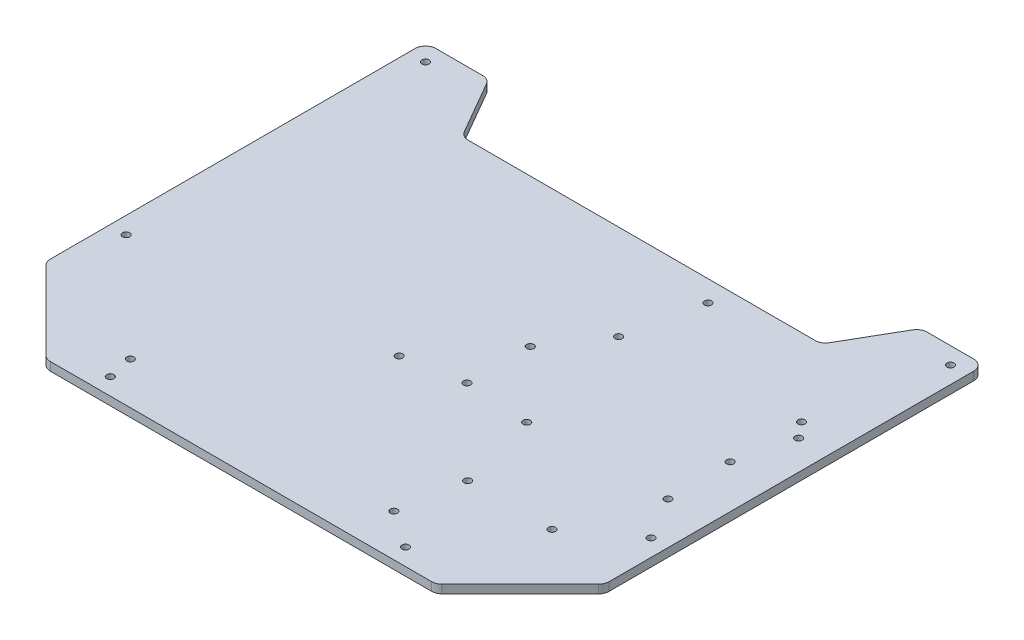
SolidWorks part; units mm, degrees
material "Acier non allié"
ref_plane "Front" through (0, 0, 0) normal (0, 0, 1) x (1, 0, 0)
ref_plane "Top" through (0, 0, 0) normal (0, 1, 0) x (1, 0, 0)
ref_plane "Right" through (0, 0, 0) normal (1, 0, 0) x (0, 0, -1)
sketch "Main scetch" plane through (0, 0, 0) normal (0, 1, 0) x (1, 0, 0)
  line L1 (0, 0) -> (132.5, 0) construction
  line L2 (0, 0) -> (0, 220) construction
  line L3 (0, 220) -> (132.5, 220) construction
  line L4 (132.5, 0) -> (132.5, 220) construction
  line L13 (-92.5, 0) -> (92.5, 0)
  line L14 (92.5, 0) -> (132.5, 40)
  line L15 (132.5, 40) -> (132.5, 220)
  line L16 (132.5, 220) -> (102.5, 220)
  line L17 (102.5, 220) -> (85.1795, 190)
  line L18 (85.1795, 190) -> (-85.1795, 190)
  line L19 (-102.5, 220) -> (-85.1795, 190)
  line L20 (-132.5, 220) -> (-102.5, 220)
  line L21 (-132.5, 40) -> (-132.5, 220)
  line L22 (-92.5, 0) -> (-132.5, 40)
  point P11 (0, 190)
  dimension "132.5" = 132.5
  dimension "D2" = 220
  dimension "D1" = 40
  dimension "D3" = 40
  dimension "D4" = 30
  dimension "D5" = 60
  dimension "D6" = 30
extrude "Main extrusion" add sketch "Main scetch" along normal blind 4
fillet "Congé1" radius 5 10 edges at (-132.5, 2, -40) (-92.5, 2, 0) (92.5, 2, 0) (132.5, 2, -40) (132.5, 2, -220) (102.5, 2, -220) (85.1795, 2, -190) (-85.1795, 2, -190) (-102.5, 2, -220) (-132.5, 2, -220)
sketch "Esquisse1" plane through (0, 4, 0) normal (0, 1, 0) x (1, 0, 0)
  line L0 (0, 0) -> (0, 218.5516) construction
  line L1 (132.5, 42.0711) -> (132.5, 215) construction
  line L2 (127.5, 220) -> (105.3868, 220) construction
  line L3 (-90.4289, 0) -> (90.4289, 0) construction
  circle A0 centre (70, 8) radius 1
  circle A1 centre (124.5, 70) radius 1
  circle A2 centre (124.5, 212) radius 1
  circle A3 centre (-124.5, 212) radius 1
  circle A4 centre (-124.5, 70) radius 1
  circle A5 centre (-70, 8) radius 1
  dimension "D1" = 2
  dimension "D2" = 2
  dimension "D3" = 2
  dimension "D4" = 8
  dimension "D5" = 8
  dimension "D6" = 8
  dimension "D7" = 8
  dimension "D8" = 70
  dimension "D9" = 70
extrude "Enlèv. mat.-Extru.1" cut sketch "Esquisse1" against normal through all
hole_wizard "Dégagement M31" positions "Esquisse2" profile "Esquisse3" hole size "M3" standard "ISO" end condition through all
sketch "Esquisse2" plane through (0, 4, 0) normal (0, 1, 0) x (1, 0, 0)
  point P0 (-124.5, 212)
  point P3 (-124.5, 70)
  point P6 (-70, 8)
  point P9 (70, 8)
  point P12 (124.5, 70)
  point P15 (124.5, 212)
sketch "Esquisse3" plane through (-124.5, 4, -212) normal (1, 0, 0) x (0, 0, 1)
  line L0 (0, 0) -> (0, 4)
  line L1 (0, 4) -> (1.7, 4)
  line L2 (1.7, 4) -> (1.7, 0)
  line L5 (1.7, 0) -> (0, 0)
  line L11 (0, -6.35) -> (0, 107.95) construction
  dimension "Diamètre du perçage jusqu'au prochain" = 3.4
  dimension "Profondeur du perçage jusqu'au prochain" = 4
sketch "Esquisse4" plane through (0, 4, 0) normal (0, 1, 0) x (1, 0, 0)
  line L0 (-132.5, 215) -> (-132.5, 42.0711) construction
  line L2 (82.2927, 190) -> (-82.2927, 190) construction
  line L3 (132.5, 42.0711) -> (132.5, 215) construction
  line L4 (-90.4289, 0) -> (90.4289, 0) construction
  line L5 (127.5, 220) -> (105.3868, 220) construction
  circle A5 centre (41.5, 180) radius 1
  circle A6 centre (34.12, 145) radius 1
  circle A7 centre (112.5, 153.32) radius 1
  circle A8 centre (118.5, 146) radius 1
  circle A9 centre (112, 120) radius 1
  circle A10 centre (112.5, 90) radius 1
  circle A11 centre (17.2, 120) radius 1
  circle A12 centre (17.2, 90) radius 1
  circle A13 centre (47.5, 88) radius 1
  circle A14 centre (57.5, 50) radius 1
  circle A15 centre (97.5, 50) radius 1
  circle A16 centre (52.5, 20) radius 1
  circle A17 centre (-10, 85) radius 1
  circle A18 centre (-72.5, 20) radius 1
  dimension "D13" = 2
  dimension "D16" = 2
  dimension "D19" = 2
  dimension "D24" = 2
  dimension "D25" = 2
  dimension "D28" = 2
  dimension "D30" = 2
  dimension "D32" = 2
  dimension "D36" = 2
  dimension "D37" = 2
  dimension "D40" = 2
  dimension "D48" = 2
  dimension "D49" = 2
  dimension "D50" = 2
  dimension "D14" = 174
  dimension "D15" = 10
  dimension "D17" = 166.62
  dimension "D18" = 45
  dimension "D20" = 20
  dimension "D21" = 66.68
  dimension "D22" = 14
  dimension "D23" = 74
  dimension "D26" = 20.5
  dimension "D27" = 100
  dimension "D29" = 30
  dimension "D31" = 115.3
  dimension "D33" = 115.3
  dimension "D34" = 132
  dimension "D35" = 85
  dimension "D38" = 50
  dimension "D39" = 75
  dimension "D41" = 35
  dimension "D42" = 80
  dimension "D43" = 20
  dimension "D44" = 20
  dimension "D45" = 205
  dimension "D46" = 85
  dimension "D47" = 142.5
extrude "Enlèv. mat.-Extru.2" cut sketch "Esquisse4" against normal through all
hole_wizard "Dégagement M32" positions "Esquisse5" profile "Esquisse6" hole size "M3" standard "ISO" end condition through all
sketch "Esquisse5" plane through (0, 4, 0) normal (0, 1, 0) x (1, 0, 0)
  point P9 (17.2, 120)
  point P18 (34.12, 145)
  point P21 (41.5, 180)
  point P24 (112.5, 153.32)
  point P27 (118.5, 146)
  point P30 (112, 120)
  point P33 (112.5, 90)
  point P36 (47.5, 88)
  point P39 (17.2, 90)
  point P42 (57.5, 50)
  point P45 (97.5, 50)
  point P48 (-10, 85)
  point P51 (-72.5, 20)
  point P54 (52.5, 20)
  point P57 (0, 0)
  point P58 (0, 0)
  point P59 (0, 0)
  point P60 (0, 0)
  point P61 (0, 0)
sketch "Esquisse6" plane through (17.2, 4, -120) normal (1, 0, 0) x (0, 0, 1)
  line L0 (0, 0) -> (0, 4)
  line L1 (0, 4) -> (1.7, 4)
  line L2 (1.7, 4) -> (1.7, 0)
  line L5 (1.7, 0) -> (0, 0)
  line L11 (0, -6.35) -> (0, 107.95) construction
  dimension "Diamètre du perçage jusqu'au prochain" = 3.4
  dimension "Profondeur du perçage jusqu'au prochain" = 4
equation "\"WIDTH\"= 300mm'Total width of the robot"
equation "\"LENGTH\"= 220mm'Total length of the robot"
equation "\"D2@Main scetch\" = \"LENGTH\""
equation "\"CUT_DEPTH\"= 45mm'Depth of the cut on the edges of the plate"
equation "\"Plate_th\"= 3mm'Thickness of the plate"
equation "\"D1\"= \"Plate_th\""
equation "\"D47@Esquisse4\"=(80+205)/2"
